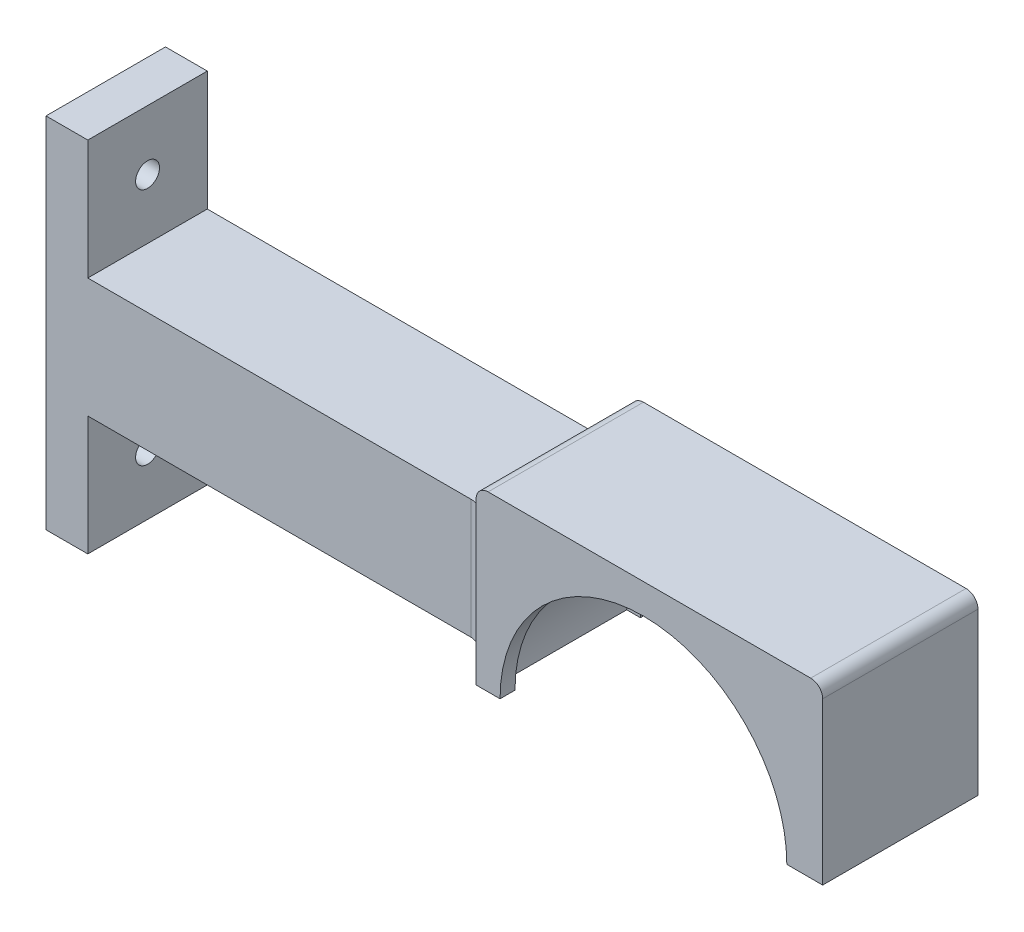
SolidWorks part; units mm, degrees
ref_plane "정면" through (0, 0, 0) normal (0, 0, 1) x (1, 0, 0)
ref_plane "윗면" through (0, 0, 0) normal (0, 1, 0) x (1, 0, 0)
ref_plane "우측면" through (0, 0, 0) normal (1, 0, 0) x (0, 0, -1)
sketch "스케치5" plane through (0, 0, 0) normal (0, 1, 0) x (1, 0, 0)
  line L1 (-14, -6.5) -> (14, -6.5)
  line L2 (-14, -6.5) -> (-14, 6.5)
  line L3 (-14, 6.5) -> (14, 6.5)
  line L4 (14, -6.5) -> (14, 6.5)
  line L5 (-14, -6.5) -> (14, 6.5) construction
  line L6 (-14, 6.5) -> (14, -6.5) construction
  point P0 (0, 0)
  dimension "D1" = 28
  dimension "D2" = 13
extrude "보스-돌출4" add sketch "스케치5" along normal blind 13.5
sketch "스케치6" plane through (0, 0, 0) normal (0, -1, 0) x (1, 0, 0)
  line L0 (0, 5.5) -> (0, -5.5) construction
  line L1 (0, -5.5) -> (13.15, -5.5) construction
  line L2 (13.15, -5.5) -> (0, 5.5) construction
  line L3 (0, 5.5) -> (13.15, 5.5) construction
  line L4 (13.15, -5.5) -> (13.15, 5.5) construction
  line L5 (0, 0) -> (13.15, 5.5) construction
  line L6 (0, 0) -> (13.15, -5.5) construction
  line L8 (13.15, -5.25) -> (0, -5.25)
  line L9 (13.15, -5.25) -> (13.15, 5.25)
  line L10 (13.15, 5.25) -> (0, 5.25)
  line L11 (0, -5.25) -> (0, 5.25)
  line L12 (13.15, -5.25) -> (0, 5.25) construction
  line L13 (13.15, 5.25) -> (0, -5.25) construction
  point P0 (0, 0)
  point P2 (6.575, 0)
  dimension "D1" = 13.15
  dimension "D2" = 11
  dimension "D3" = 10.5
  dimension "D4" = 13.15
sketch "스케치7" plane through (0, 0, 6.5) normal (0, 0, 1) x (1, 0, 0)
  line L0 (-14, 0) -> (14, 0) construction
  circle A0 centre (0, 0) radius 13.15
  dimension "D1" = 26.3
sweep "컷-스윕1" cut profiles "스케치6" path "스케치7"
sketch "스케치8" plane through (0, 0, 6.5) normal (0, 0, 1) x (1, 0, 0)
  line L0 (-14, 0) -> (14, 0) construction
  circle A0 centre (0, 0) radius 12
  dimension "D1" = 24
extrude "컷-돌출1" cut sketch "스케치8" against normal blind 13
sketch "스케치9" plane through (0, 13.5, 0) normal (0, 1, 0) x (1, 0, 0)
  line L1 (14, -6.5) -> (-14, -6.5)
  line L2 (14, -6.5) -> (14, 6.5)
  line L3 (14, 6.5) -> (-14, 6.5)
  line L4 (-14, -6.5) -> (-14, 6.5)
  line L5 (14, -6.5) -> (-14, 6.5) construction
  line L6 (14, 6.5) -> (-14, -6.5) construction
  point P0 (0, 0)
extrude "보스-돌출5" add sketch "스케치9" along normal blind 1
sketch "스케치11" plane through (14, 0, 0) normal (1, 0, 0) x (0, 0, -1)
  line L1 (6.5, 0) -> (-6.5, 0)
  line L2 (6.5, 0) -> (6.5, 14.5)
  line L3 (6.5, 14.5) -> (-6.5, 14.5)
  line L4 (-6.5, 0) -> (-6.5, 14.5)
extrude "보스-돌출6" add sketch "스케치11" along normal blind 1
fillet "필렛1" radius 1 2 edges at (15, 14.5, 0) (-14, 14.5, 0)
sketch "스케치12" plane through (-14, 0, 0) normal (-1, 0, 0) x (0, 0, 1)
  line L0 (-6.5, 13.5) -> (6.5, 0) construction
  line L2 (-5, 11.75) -> (5, 11.75)
  line L3 (-5, 11.75) -> (-5, 1.75)
  line L4 (-5, 1.75) -> (5, 1.75)
  line L5 (5, 11.75) -> (5, 1.75)
  line L6 (-5, 11.75) -> (5, 1.75) construction
  line L7 (-5, 1.75) -> (5, 11.75) construction
  point P4 (0, 6.75)
  dimension "D1" = 10
  dimension "D2" = 10
extrude "보스-돌출7" add sketch "스케치12" along normal blind 37.5
sketch "스케치13" plane through (-51.5, 0, 0) normal (-1, 0, 0) x (0, 0, 1)
  line L0 (5, 11.75) -> (-5, 1.75) construction
  line L1 (5, 21.75) -> (-5, 11.75) construction
  line L2 (-5, 21.75) -> (5, 21.75)
  line L3 (-5, 21.75) -> (-5, -8.25)
  line L4 (-5, -8.25) -> (5, -8.25)
  line L5 (5, 21.75) -> (5, -8.25)
  line L6 (-5, 21.75) -> (5, -8.25) construction
  line L7 (-5, -8.25) -> (5, 21.75) construction
  line L8 (-5, 1.75) -> (5, -8.25) construction
  circle A0 centre (0, 16.75) radius 1
  circle A1 centre (0, -3.25) radius 1
  point P4 (0, 6.75)
  dimension "D1" = 30
extrude "보스-돌출8" add sketch "스케치13" against normal blind 3.5
fillet "필렛2" radius 2 3 edges at (-14, 6.75, -5) (-14, 6.75, 5) (-14, 1.75, 0)
fillet "필렛3" radius 1 1 edges at (-14, 11.75, 0)
